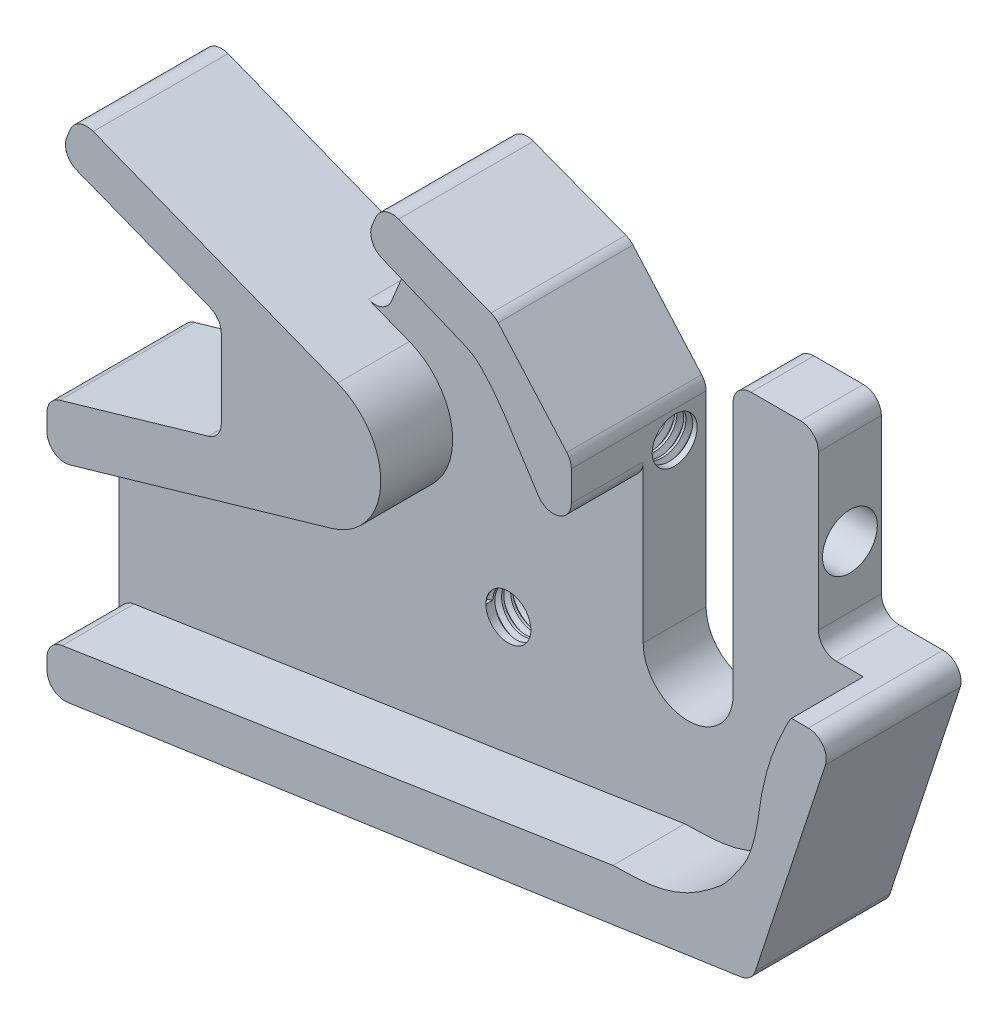
SolidWorks part; units mm, degrees
ref_plane "Front Plane" through (0, 0, 0) normal (0, 0, 1) x (1, 0, 0)
ref_plane "Top Plane" through (0, 0, 0) normal (0, 1, 0) x (1, 0, 0)
ref_plane "Right Plane" through (0, 0, 0) normal (1, 0, 0) x (0, 0, -1)
sketch "Sketch1" plane through (0, 0, 0) normal (0, 0, 1) x (1, 0, 0)
  line L0 (169.0465, 531.5792) -> (1384.9618, 942.3347) construction
  line L1 (17.1755, 0.269) -> (145.8355, -18.3486) construction
  line L2 (78.9683, 43.5936) -> (88.9683, 43.5936)
  line L3 (88.9683, 43.5936) -> (88.9683, 26.5936)
  line L4 (88.9683, 26.5936) -> (78.9683, 26.5936)
  line L5 (78.9683, 26.5936) -> (78.9683, 43.5936)
  line L6 (77.9414, 43.8024) -> (71.5407, 53.8656)
  line L7 (56.0381, 62.9033) -> (67.1668, 58.333)
  line L8 (88.9683, 43.5936) -> (88.9683, 61.7655)
  line L9 (88.9683, 61.7655) -> (98.4683, 61.7655)
  line L10 (77.9414, 43.8024) -> (78.9683, 42.1878)
  line L11 (20.6229, 24.1202) -> (53.1029, 33.5417)
  line L12 (23.9133, 59.0209) -> (55.1963, 46.7648)
  line L13 (56.0381, 62.9033) -> (50.2123, 48.7174)
  line L15 (20.6228, 1.5127) -> (20.6229, 24.1202)
  line L16 (20.6229, 24.1202) -> (20.6229, 30.1202)
  line L17 (103.2745, 61.7655) -> (98.4683, 61.7655)
  line L18 (20.6229, 30.1202) -> (43.6301, 36.7939)
  line L19 (23.9133, 59.0209) -> (22.0894, 54.3655)
  line L20 (22.0894, 54.3655) -> (44.4958, 45.587)
  line L21 (78.9683, 43.5936) -> (78.9683, 49.2858)
  line L22 (57.9376, 67.5285) -> (70.5008, 62.7543)
  line L23 (68.2195, 57.2049) -> (70.5008, 62.7543)
  line L24 (40.0198, 35.7467) -> (40.0198, 47.3406)
  line L25 (77.3776, 54.951) -> (70.5008, 62.7543)
  line L26 (56.0381, 62.9033) -> (57.9376, 67.5285)
  line L27 (103.0983, 40.5847) -> (108.0983, 40.5847)
  line L29 (108.0983, 40.5847) -> (99.0557, 13.0352)
  line L30 (98.4683, 61.7655) -> (98.4683, 40.5847)
  line L31 (99.0557, 13.0352) -> (20.6228, 1.5127)
  line L32 (83.9683, 43.5936) -> (83.9683, 46.6936)
  line L33 (20.6228, 6.4639) -> (20.6228, 6.7639)
  line L34 (20.6228, 6.7639) -> (83.6, 16.4882)
  line L38 (78.9683, 49.2858) -> (78.9683, 52.8143)
  line L39 (77.3776, 54.951) -> (78.9683, 53.146)
  line L46 (78.9683, 53.146) -> (78.9683, 52.8143)
  line L47 (98.4683, 40.5847) -> (103.0983, 40.5847)
  circle A0 centre (83.9683, 31.5936) radius 5
  circle A1 centre (83.9683, 38.5936) radius 5
  circle A5 centre (50.1903, 40.5872) radius 7.578
  circle A6 centre (103.2745, 54.3655) radius 4.4
  circle A7 centre (103.2745, 54.3655) radius 7.4
  spline S0 degree 3 poles (67.1668, 58.333) (67.5307, 58.1482) (68.2163, 57.8297) (69.7375, 56.3376) (70.7671, 54.998) (71.5407, 53.8656) knots 0 0 0 0 0.194176 0.353383 1 1 1 1
  spline S1 degree 3 poles (83.6, 16.4882) (85.4172, 16.5376) (87.878, 16.5192) (90.6726, 17.4205) (92.3949, 18.1773) (94.0998, 19.3373) (95.7619, 20.5842) (96.8381, 21.8934) (97.5722, 23.0215) (98.2993, 24.0127) (98.8168, 25.1807) (99.3382, 26.7948) (99.7545, 28.7331) (99.9792, 30.8782) (100.4112, 32.873) (100.8434, 34.6928) (101.4168, 36.2088) (101.8572, 37.4461) (102.3579, 38.4137) (102.8418, 39.501) (103.1664, 40.2034) (103.4635, 40.5847) knots 0 0 0 0 0.157669 0.206742 0.251675 0.318971 0.383622 0.429475 0.463745 0.499497 0.534829 0.572978 0.645345 0.704784 0.75829 0.820777 0.865343 0.897594 0.933603 0.958853 1 1 1 1
  spline S2 degree 3 poles (103.5353, 40.5847) (103.5737, 40.7076) (103.6552, 40.9276) (103.7812, 41.1886) (104.0315, 41.5757) (104.2848, 42.0416) (104.6132, 42.664) (105.0506, 43.3284) (105.5376, 44.1633) (106.1189, 44.9679) (106.7473, 45.8247) (107.3304, 46.576) (107.8594, 47.2965) (108.3783, 47.8664) (108.8492, 48.4246) (109.2415, 48.9281) (109.5877, 49.4941) (110.1609, 50.7991) (110.3778, 52.0388) (110.5419, 52.9707) knots 0 0 0 0 0.030124 0.037916 0.077919 0.112151 0.152793 0.222708 0.278209 0.35365 0.429114 0.499348 0.551579 0.614984 0.65957 0.703571 0.747698 0.797187 1 1 1 1
  point P63 (0, 0)
  point P85 (103.2745, 54.3655)
  point P87 (0, 0)
  point P89 (0, 0)
  point P91 (110.3438, 51.2666)
  point P93 (109.2314, 48.9346)
  point P95 (110.5419, 52.9707)
  dimension "D5" = 8.8
  dimension "D6" = 14.8
  dimension "D1" = 130
  dimension "D2" = 10
  dimension "D3" = 17
  dimension "D4" = 9.5
extrude "Boss-Extrude1" add sketch "Sketch1" along normal blind 7 contours S1 L27 L47 L30 A7 L9 L8 L3 L4 L5 L10 L6 S0 L7 L13 L12 A5 L11 L15 | L30 A7 | A0 L4 L3 | A0 L5 L4 region at (63.5097, 30.8173, 0) region at (87.8514, 27.7104, 0) region at (80.0851, 27.7104, 0) region at (97.4134, 54.3655, 0)
extrude "Boss-Extrude2" add sketch "Sketch1<3>" along normal blind 15 contours A5 L12 L19 L20 | A5 | A5 L20 L24 L18 | A5 L18 L16 L11 | S1 L31 L29 L27 | L23 S0 L6 L10 L5 L21 L38 L46 L39 L25 | L7 S0 L23 L22 L26 region at (74.5437, 53.5182, 0) region at (63.3137, 62.7114, 0) region at (35.1841, 52.0124, 0) region at (69.2098, 14.0817, 0) region at (50.1903, 40.5872, 0) region at (41.5617, 41.668, 0) region at (33.5189, 30.7275, 0)
sketch "Sketch1<3>" plane through (0, 0, 0) normal (0, 0, 1) x (1, 0, 0) same geometry as "Sketch1"
fillet "Fillet1" radius 2 19 edges at (78.9683, 53.146, 7.5) (70.5008, 62.7543, 7.5) (99.0557, 13.0352, 7.5) (108.0983, 40.5847, 7.5) (98.4683, 61.7655, 3.5) (88.9683, 61.7655, 3.5) (57.9376, 67.5285, 7.5) (56.0381, 62.9033, 11) (78.9683, 42.1878, 11) (20.6229, 24.1202, 11) (20.6229, 30.1202, 7.5) (23.9133, 59.0209, 7.5) (22.0894, 54.3655, 7.5) (40.0198, 47.3406, 7.5) (40.0198, 35.7467, 7.5) (20.6228, 1.5127, 7.5) (50.2123, 48.7174, 3.5) (98.4683, 40.5847, 3.5) (20.6228, 6.7639, 11)
sketch "Sketch4" plane through (88.9683, 0, 0) normal (-1, 0, 0) x (0, 0, 1)
  line L0 (3.5, 31.5936) -> (3.5, 49.3936)
  line L1 (7, 31.5936) -> (0, 31.5936) construction
  circle A0 centre (3.5, 49.3936) radius 3.05
  dimension "D1" = 17.8
extrude "Cut-Extrude2" cut sketch "Sketch4" against normal blind 30 contours A0 region at (88.9683, 47.2979, 5.5957)
hole_wizard "Tap Drill for M6x1.0 Tap3" positions "3DSketch7" profile "Sketch10" hole size "M6x1.0" standard "ANSI Metric"
sketch3d "3DSketch7"
  line L0 (98.4683, 49.3936, 3.5) -> (88.9683, 49.3936, 3.5) construction
  point P0 (88.9683, 49.3936, 3.5)
sketch "Sketch10" plane through (88.9683, 49.3936, 3.5) normal (0, 1, 0) x (0, 0, -1)
  line L0 (0, 0) -> (0, 31.5022)
  line L1 (0, 31.5022) -> (2.5, 30)
  line L2 (2.5, 30) -> (2.5, 0)
  line L5 (2.5, 0) -> (0, 0)
  line L10 (0, 31.5022) -> (-2.5, 30) construction
  line L11 (0, -6.35) -> (0, 107.95) construction
  dimension "Hole Dia." = 5
  dimension "Hole Depth" = 30
  dimension "Drill Angle" = 118
thread "Thread2" pitch 1 method cut profile "Thread Profile2" start angle 0, offset 0, length 20, pitch 1, diameter 5
ref_plane "Plane2" through (78.9683, 49.3936, 6) normal (0, -1, 0) x (0, 0, 1)
sketch "Thread Profile2" plane through (78.9683, 49.3936, 6) normal (0, -1, 0) x (0, 0, 1)
  line L0 (0, 0) -> (0, 1) construction
  line L1 (0, 0) -> (0.5413, 0.3125)
  line L2 (0.5413, 0.3125) -> (0.5413, 0.4375)
  line L3 (0.5413, 0.4375) -> (0, 0.75)
  line L4 (0.5413, 0.375) -> (0, 0.375) construction
  line L11 (0, 0) -> (0, 0.75)
  point P2 (0, 0)
  dimension "Pitch" = 1
  dimension "Profile_Angle" = 60
  dimension "Profile_Land" = 0.125
  dimension "Profile_Height" = 0.5413
sketch "Sketch14" plane through (0, 0, 7) normal (0, 0, 1) x (1, 0, 0)
  line L0 (83.9683, 26.5936) -> (63.9683, 26.5936)
  arc A0 (78.9683, 31.5936) -> (88.9683, 31.5936) centre (83.9683, 31.5936) ccw construction
hole_wizard "Tap Drill for M6x1.0 Tap4" positions "3DSketch11" profile "Sketch15" hole size "M6x1.0" standard "ANSI Metric"
sketch3d "3DSketch11"
  point P0 (63.9683, 26.5936, 7)
sketch "Sketch15" plane through (63.9683, 26.5936, 7) normal (1, 0, 0) x (0, -1, 0)
  line L0 (0, 0) -> (0, 31.5022)
  line L1 (0, 31.5022) -> (2.5, 30)
  line L2 (2.5, 30) -> (2.5, 0)
  line L5 (2.5, 0) -> (0, 0)
  line L10 (0, 31.5022) -> (-2.5, 30) construction
  line L11 (0, -6.35) -> (0, 107.95) construction
  dimension "Hole Dia." = 5
  dimension "Hole Depth" = 30
  dimension "Drill Angle" = 118
thread "Thread3" pitch 1 method cut profile "Thread Profile3" start angle 0, offset 0, length 20, pitch 1, diameter 5
ref_plane "Plane3" through (61.4683, 26.5936, 7) normal (0, -1, 0) x (-1, 0, 0)
sketch "Thread Profile3" plane through (61.4683, 26.5936, 7) normal (0, -1, 0) x (-1, 0, 0)
  line L0 (0, 0) -> (0, 1) construction
  line L1 (0, 0) -> (0.5413, 0.3125)
  line L2 (0.5413, 0.3125) -> (0.5413, 0.4375)
  line L3 (0.5413, 0.4375) -> (0, 0.75)
  line L4 (0.5413, 0.375) -> (0, 0.375) construction
  line L11 (0, 0) -> (0, 0.75)
  point P2 (0, 0)
  dimension "Pitch" = 1
  dimension "Profile_Angle" = 60
  dimension "Profile_Land" = 0.125
  dimension "Profile_Height" = 0.5413
